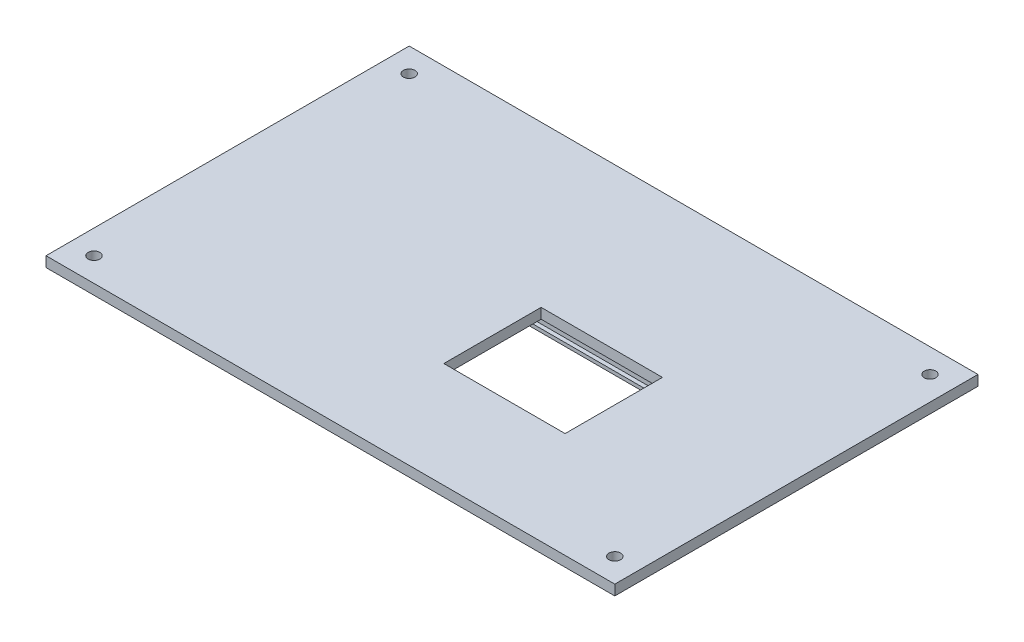
SolidWorks part; units mm, degrees
material "PETG"
ref_plane "Front Plane" through (0, 0, 0) normal (0, 0, 1) x (1, 0, 0)
ref_plane "Top Plane" through (0, 0, 0) normal (0, 1, 0) x (1, 0, 0)
ref_plane "Right Plane" through (0, 0, 0) normal (1, 0, 0) x (0, 0, -1)
other "Configuration Table"
sketch "Sketch1" plane through (0, 0, 0) normal (0, 1, 0) x (1, 0, 0)
  line L0 (-83, -53) -> (83, -53)
  line L1 (83, -53) -> (83, 53)
  line L2 (83, 53) -> (-83, 53)
  line L3 (-83, 53) -> (-83, -53)
extrude "Lid_Plate" add sketch "Sketch1" along normal blind 3 from offset 88
sketch "Sketch2" plane through (0, 0, 0) normal (0, 1, 0) x (1, 0, 0)
  line L1 (2.3, -22.2) -> (37.7, -22.2)
  line L2 (2.3, -22.2) -> (2.3, 6.2)
  line L3 (2.3, 6.2) -> (37.7, 6.2)
  line L4 (37.7, -22.2) -> (37.7, 6.2)
  line L5 (2.3, -22.2) -> (37.7, 6.2) construction
  line L6 (2.3, 6.2) -> (37.7, -22.2) construction
  point P5 (20, -8)
  dimension "D1" = 35.4
  dimension "D2" = 28.4
extrude "TFT_Window" cut sketch "Sketch2" along normal through all and the other way through all
sketch "Sketch3" plane through (0, 0, 0) normal (0, 1, 0) x (1, 0, 0)
  circle A0 centre (-76, 46) radius 1.7
  circle A1 centre (-76, -46) radius 1.7
  circle A2 centre (76, 46) radius 1.7
  circle A3 centre (76, -46) radius 1.7
  dimension "D1" = 3.4
  dimension "D2" = 3.4
  dimension "D3" = 3.4
  dimension "D4" = 3.4
extrude "Lid_Screw_Holes_M3" cut sketch "Sketch3" along normal through all and the other way through all
sketch "Sketch4" plane through (0, 0, 0) normal (0, 1, 0) x (1, 0, 0)
  line L0 (-4, 9.8) -> (44, 9.8)
  line L1 (44, 9.8) -> (44, 11.8)
  line L2 (44, 11.8) -> (-4, 11.8)
  line L3 (-4, 11.8) -> (-4, 9.8)
  line L4 (-4, -27.8) -> (44, -27.8)
  line L5 (44, -27.8) -> (44, -25.8)
  line L6 (44, -25.8) -> (-4, -25.8)
  line L7 (-4, -25.8) -> (-4, -27.8)
extrude "TFT_Rails" add sketch "Sketch4" against normal blind 5.8 from offset 88
sketch "Sketch5" plane through (0, 0, 0) normal (0, 1, 0) x (1, 0, 0)
  line L0 (-4, 8.6) -> (44, 8.6)
  line L1 (44, 8.6) -> (44, 9.8)
  line L2 (44, 9.8) -> (-4, 9.8)
  line L3 (-4, 9.8) -> (-4, 8.6)
  line L4 (-4, -25.8) -> (44, -25.8)
  line L5 (44, -25.8) -> (44, -24.6)
  line L6 (44, -24.6) -> (-4, -24.6)
  line L7 (-4, -24.6) -> (-4, -25.8)
extrude "TFT_Rail_Lips" add sketch "Sketch5" against normal blind 1 from offset 83.2
equation "\"Jar_OD\"= 90  'ASSUMED - Part C fallback - jar outer diameter"
equation "\"Jar_H\"= 120  'ASSUMED - Part C fallback - jar height"
equation "\"Pump_L\"= 45  'ASSUMED - Part C fallback"
equation "\"Pump_W\"= 24  'ASSUMED - Part C fallback"
equation "\"Pump_H\"= 33  'ASSUMED - Part C fallback"
equation "\"Pump_Outlet_OD\"= 7.5  'ASSUMED - Part C fallback"
equation "\"Tube_OD\"= 8  'ASSUMED - Part C fallback"
equation "\"Tube_ID\"= 6  'ASSUMED - Part C fallback"
equation "\"TDS_Body_Dia\"= 12  'ASSUMED - Part C fallback"
equation "\"TDS_Wet_Len\"= 45  'ASSUMED - Part C fallback - length in water"
equation "\"DS_Tube_Dia\"= 6  'ASSUMED - Part C fallback"
equation "\"DS_Tube_Len\"= 50  'ASSUMED - Part C fallback"
equation "\"ORP_Body_Dia\"= 12  'ASSUMED - Part C fallback"
equation "\"ORP_Body_Len\"= 150  'ASSUMED - Part C fallback"
equation "\"ORP_Cap_Dia\"= 16  'ASSUMED - Part C fallback"
equation "\"Turb_W\"= 33  'ASSUMED - Part C fallback - head width"
equation "\"Turb_D\"= 28  'ASSUMED - Part C fallback - head depth"
equation "\"Turb_H\"= 30  'ASSUMED - Part C fallback - head height"
equation "\"Turb_Slot_W\"= 10  'ASSUMED - Part C fallback - slot width"
equation "\"Flow_L\"= 62  'ASSUMED - Part C fallback YF-S201"
equation "\"Flow_W\"= 36  'ASSUMED - Part C fallback"
equation "\"Flow_H\"= 35  'ASSUMED - Part C fallback"
equation "\"Thread_G12_OD\"= 20.955  'ASSUMED - Part C fallback thread G1/2 (major diameter)"
equation "\"Valve_L\"= 75  'ASSUMED - Part C fallback"
equation "\"Valve_W\"= 45  'ASSUMED - Part C fallback"
equation "\"Valve_H\"= 60  'ASSUMED - Part C fallback"
equation "\"Tee_L\"= 40  'ASSUMED - Part C fallback - overall length"
equation "\"Tee_Branch_L\"= 25  'ASSUMED - Part C fallback"
equation "\"Tee_OD\"= 12  'ASSUMED - Part C fallback"
equation "\"Cuv_W\"= 12.5  'ASSUMED - Part C fallback"
equation "\"Cuv_D\"= 12.5  'ASSUMED - Part C fallback"
equation "\"Cuv_H\"= 45  'ASSUMED - Part C fallback"
equation "\"LED_Board_L\"= 20  'ASSUMED - Part C fallback"
equation "\"LED_Board_W\"= 20  'ASSUMED - Part C fallback - LED at centre"
equation "\"GUVA_L\"= 20  'ASSUMED - Part C fallback"
equation "\"GUVA_W\"= 12  'ASSUMED - Part C fallback - sensor at centre"
equation "\"Reed_L\"= 27  'ASSUMED - Part C fallback MC-38 half"
equation "\"Reed_W\"= 14  'ASSUMED - Part C fallback"
equation "\"Reed_H\"= 8  'ASSUMED - Part C fallback"
equation "\"ESP_L\"= 51  'ASSUMED - Part C fallback"
equation "\"ESP_W\"= 28  'ASSUMED - Part C fallback"
equation "\"TFT_L\"= 58  'ASSUMED - Part C fallback - board"
equation "\"TFT_W\"= 35  'ASSUMED - Part C fallback - board"
equation "\"TFT_Win_L\"= 35  'ASSUMED - Part C fallback - visible window"
equation "\"TFT_Win_W\"= 28  'ASSUMED - Part C fallback - visible window"
equation "\"Relay_L\"= 50  'ASSUMED - Part C fallback"
equation "\"Relay_W\"= 26  'ASSUMED - Part C fallback"
equation "\"Relay_H\"= 19  'ASSUMED - Part C fallback"
equation "\"Mosfet_L\"= 34  'ASSUMED - Part C fallback"
equation "\"Mosfet_W\"= 17  'ASSUMED - Part C fallback"
equation "\"Mosfet_H\"= 12  'ASSUMED - Part C fallback"
equation "\"TDS_Board_L\"= 42  'ASSUMED - Part C fallback"
equation "\"TDS_Board_W\"= 32  'ASSUMED - Part C fallback"
equation "\"Turb_Board_L\"= 38  'ASSUMED - Part C fallback"
equation "\"Turb_Board_W\"= 28  'ASSUMED - Part C fallback"
equation "\"BNC_Thread_Dia\"= 9.5  'ASSUMED - Part C fallback"
equation "\"Plate_L\"= 420  'ASSUMED - Part C fallback"
equation "\"Plate_W\"= 297  'ASSUMED - Part C fallback"
equation "\"Plate_T\"= 6  'ASSUMED - Part C fallback"
equation "\"Probe_Clr\"= 0.3  'DESIGN VALUE - Part C rule 3 - printed probe hole = diameter + 0.3"
equation "\"Cuv_Clr\"= 0.2  'DESIGN VALUE - Part C rule 3 - cuvette pocket = size + 0.2"
equation "\"Label_H\"= 0.6  'DESIGN VALUE - Part D - raised label height"
equation "\"D1@Sketch2\" = \"TFT_Win_L\" + 0.4"
equation "\"D2@Sketch2\" = \"TFT_Win_W\" + 0.4"
